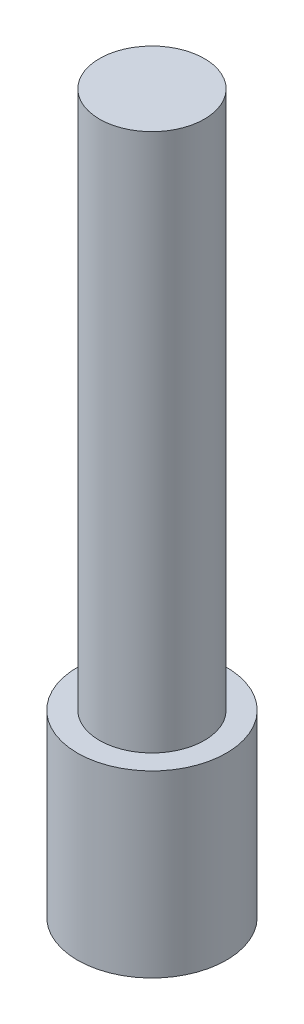
SolidWorks part; units mm, degrees
ref_plane "Front Plane" through (0, 0, 0) normal (0, 0, 1) x (1, 0, 0)
ref_plane "Top Plane" through (0, 0, 0) normal (0, 1, 0) x (1, 0, 0)
ref_plane "Right Plane" through (0, 0, 0) normal (1, 0, 0) x (0, 0, -1)
sketch "Sketch2" plane through (0, 0, 0) normal (0, 1, 0) x (1, 0, 0)
  circle A0 centre (0, 0) radius 4.15
  circle A1 centre (0, 0) radius 2.925
  dimension "D1" = 8.3
  dimension "D2" = 5.85
extrude "Boss-Extrude1" add sketch "Sketch2" along normal blind 30 contours A1
extrude "Boss-Extrude2" add sketch "Sketch2<3>" against normal blind 10 separate body
sketch "Sketch2<3>" plane through (0, 0, 0) normal (0, 1, 0) x (1, 0, 0) same geometry as "Sketch2"
